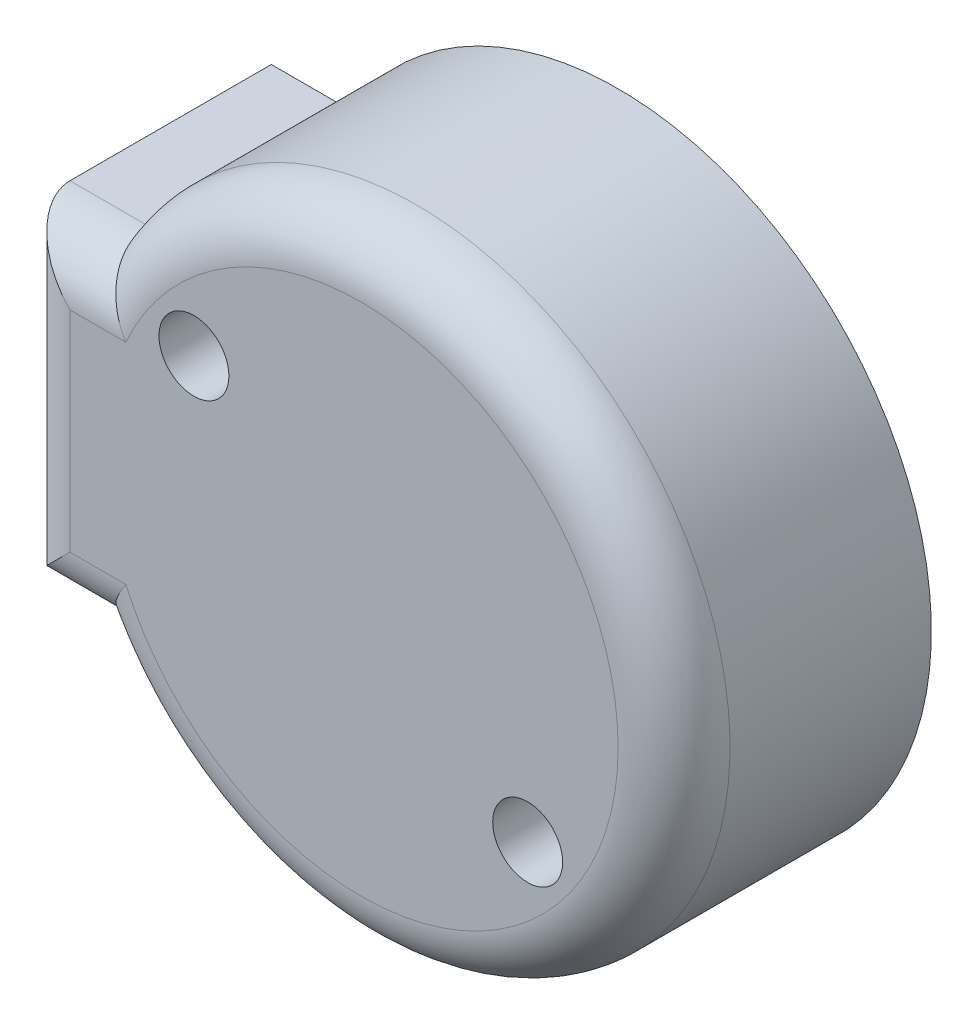
SolidWorks part; units mm, degrees
ref_plane "Front Plane" through (0, 0, 0) normal (0, 0, 1) x (1, 0, 0)
ref_plane "Top Plane" through (0, 0, 0) normal (0, 1, 0) x (1, 0, 0)
ref_plane "Right Plane" through (0, 0, 0) normal (1, 0, 0) x (0, 0, -1)
sketch "Sketch1" plane through (0, 0, 0) normal (0, 0, 1) x (1, 0, 0)
  circle A0 centre (0, 0) radius 14.224
  circle A1 centre (0, 0) radius 9.525 construction
  dimension "D1" = 28.448
  dimension "D2" = 19.05
extrude "Boss-Extrude1" add sketch "Sketch1" along normal blind 11.684
sketch "Sketch2" plane through (0, 0, 11.684) normal (0, 0, 1) x (1, 0, 0)
  line L0 (-15.748, 0) -> (0, 0) construction
  line L2 (-15.748, 7.3025) -> (-4.8856, 7.3025)
  line L3 (-15.748, 7.3025) -> (-15.748, -7.3025)
  line L4 (-15.748, -7.3025) -> (-4.8856, -7.3025)
  line L5 (-4.8856, 7.3025) -> (-4.8856, -7.3025)
  circle A0 centre (0, 0) radius 14.224 construction
  dimension "D1" = 15.748
  dimension "D2" = 14.605
extrude "Boss-Extrude2" add sketch "Sketch2" against normal up to surface (11.684 mm away) up to face at (14.224, 0, 0)
fillet "Fillet1" radius 2.54 4 edges at (-13.9772, -7.3025, 11.684) (-15.748, 0, 11.684) (-13.9772, 7.3025, 11.684) (14.224, 0, 11.684)
sketch "Sketch3" plane through (0, 0, 0) normal (0, 0, -1) x (-1, 0, 0)
  line L0 (0, 0) -> (15.748, 0) construction
  line L1 (15.748, -7.3025) -> (15.748, 7.3025) construction
  line L2 (7.5769, 5.772) -> (0, 0) construction
  line L3 (0, 0) -> (-7.5769, -5.772) construction
  circle A0 centre (7.5769, 5.772) radius 1.5875
  circle A1 centre (-7.5769, -5.772) radius 1.5875
  circle A2 centre (0, 0) radius 9.525 construction
  dimension "D1" = 3.175
  dimension "D2" = 37.3
extrude "Cut-Extrude1" cut sketch "Sketch3" against normal up to surface (11.684 mm away) up to face at (-6.3503, 0, 11.684)
